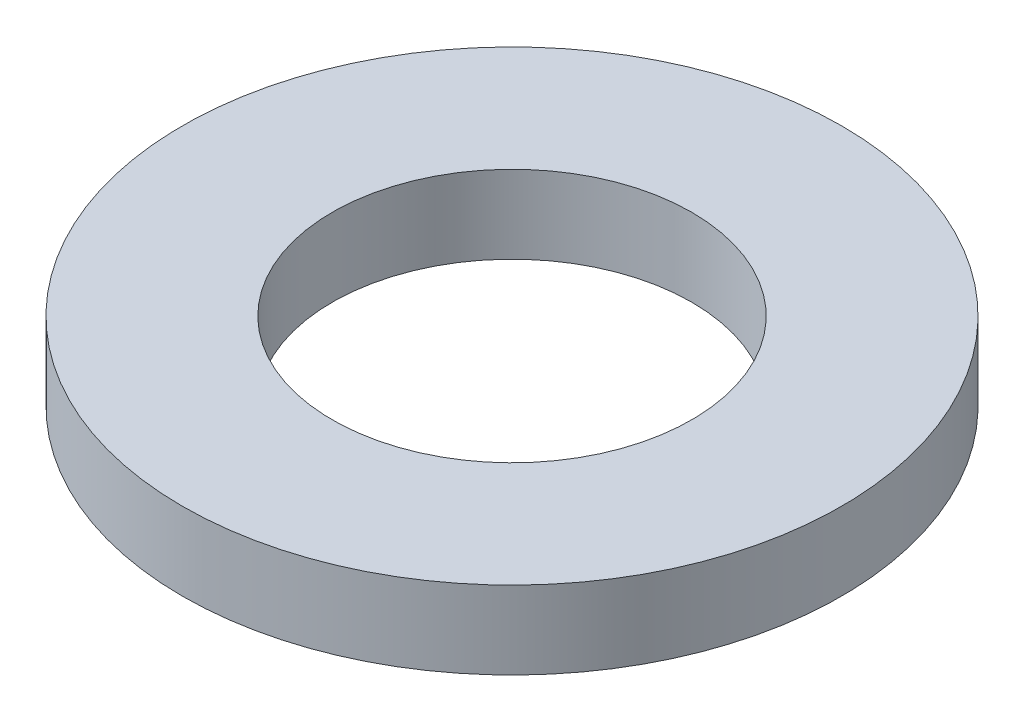
SolidWorks part; units mm, degrees
ref_plane "Front Plane" through (0, 0, 0) normal (0, 0, 1) x (1, 0, 0)
ref_plane "Top Plane" through (0, 0, 0) normal (0, 1, 0) x (1, 0, 0)
ref_plane "Right Plane" through (0, 0, 0) normal (1, 0, 0) x (0, 0, -1)
sketch "Sketch1" plane through (0, 0, 0) normal (0, 1, 0) x (1, 0, 0)
  circle A0 centre (0, 0) radius 55
  dimension "FLANGE_OD" = 110
extrude "Boss-Extrude1" add sketch "Sketch1" along normal blind 13
sketch "Sketch2" plane through (0, 0, 0) normal (0, 1, 0) x (1, 0, 0)
  circle A0 centre (0, 0) radius 30
  dimension "BORE_D" = 60
extrude "Cut-Extrude1" cut sketch "Sketch2" along normal through all
sketch "Sketch3" plane through (0, 13, 0) normal (0, 1, 0) x (1, 0, 0)
  circle A0 centre (0, 0) radius 24.0643 construction
  circle A1 centre (-24.0643, 0) radius 3.3398
  dimension "BOLT_D" = 6.6796
  dimension "BOLT_PCD" = 48.1287
extrude "Cut-Extrude2" cut sketch "Sketch3" against normal blind 8.4565 rebuild error yes
pattern_circular "CirPattern1" count 3 over 360 rebuild error yes
